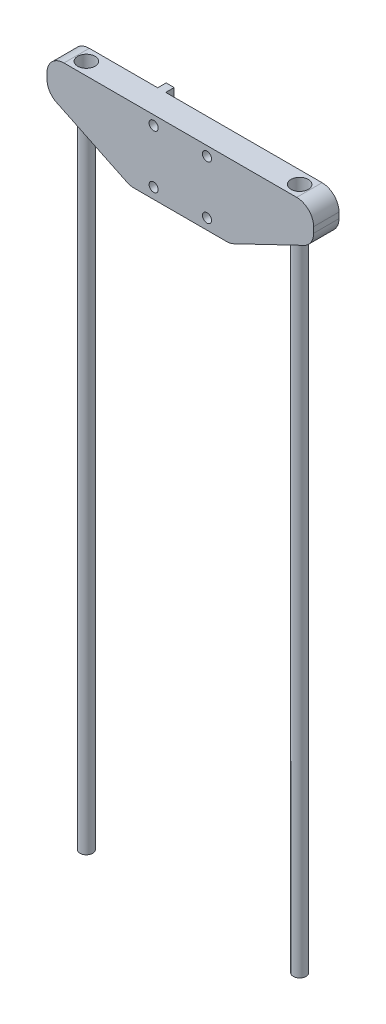
SolidWorks part; units mm, degrees
other "Markup2"
sketch "Sketch8"
other "Markup3"
sketch "Sketch15"
ref_plane "Front Plane" through (0, 0, 0) normal (0, 0, 1) x (1, 0, 0)
ref_plane "Top Plane" through (0, 0, 0) normal (0, 1, 0) x (1, 0, 0)
ref_plane "Right Plane" through (0, 0, 0) normal (1, 0, 0) x (0, 0, -1)
sketch "Sketch2" plane through (0, 0, 0) normal (0, 0, 1) x (1, 0, 0)
  line L0 (-40, 0) -> (-40, -243.6) construction
  line L1 (40, 0) -> (40, -243.6) construction
  line L2 (0, 48.6067) -> (0, -93.2297) construction
  line L3 (-50, 12.5) -> (-50, 0)
  line L4 (-50, 0) -> (-18.75, -15)
  line L5 (-18.75, -15) -> (18.75, -15)
  line L6 (18.75, -15) -> (50, 0)
  line L7 (-50, 12.5) -> (50, 12.5)
  line L8 (50, 12.5) -> (50, 0)
  line L10 (-42.3812, 0) -> (-37.6188, 0)
  line L11 (-42.3812, 0) -> (-42.3812, -243.6)
  line L12 (-42.3812, -243.6) -> (-37.6187, -243.6)
  line L13 (-37.6188, 0) -> (-37.6187, -243.6)
  line L14 (-10, 9) -> (10, 9) construction
  line L15 (-10, 9) -> (-10, -11) construction
  line L16 (-10, -11) -> (10, -11) construction
  line L17 (10, 9) -> (10, -11) construction
  line L18 (37.6188, -243.6) -> (42.3813, -243.6)
  line L19 (37.6188, -243.6) -> (37.6188, 0)
  line L20 (37.6188, 0) -> (42.3812, 0)
  line L21 (42.3813, -243.6) -> (42.3812, 0)
  dimension "D1" = 80
  dimension "D3" = 4.7625
  dimension "D4" = 20
  dimension "D5" = 20
  dimension "D6" = 228.6
  dimension "12.5" = 12.5
  dimension "D8" = 15
  dimension "D9" = 4
  dimension "D10" = 12.5
  dimension "D11" = 100
  dimension "D12" = 37.5
sketch "Sketch9" plane through (0, 0, 0) normal (0, 1, 0) x (1, 0, 0)
  line L0 (-40, 0) -> (-35, 0) construction
  line L2 (-40, 2.3812) -> (-35, 2.3812)
  line L3 (-40, -2.3812) -> (-35, -2.3812)
  line L4 (0, 20.7896) -> (0, -26.7229) construction
  line L5 (40, 0) -> (35, 0) construction
  line L6 (40, 2.3813) -> (35, 2.3813)
  line L7 (40, -2.3813) -> (35, -2.3813)
  line L8 (-37.5, 2.3812) -> (-37.5, -2.3812) construction
  line L9 (-42.3812, 0) -> (-37.6187, 0) construction
  line L10 (37.5, 2.3813) -> (37.5, -2.3813) construction
  arc A0 (-40, 2.3812) -> (-40, -2.3812) centre (-40, 0) ccw
  arc A1 (-35, -2.3812) -> (-35, 2.3812) centre (-35, 0) ccw
  arc A2 (40, 2.3813) -> (40, -2.3813) centre (40, 0) cw
  arc A3 (35, -2.3813) -> (35, 2.3813) centre (35, 0) cw
  circle A4 centre (-40, 0) radius 1.5
  circle A5 centre (40, 0) radius 1.5
  point P5 (-37.5, 0)
  point P15 (37.5, 0)
  dimension "D1" = 5
  dimension "D3" = 3
  dimension "D2" = 4.7625
sketch "Sketch3" plane through (0, 0, 0) normal (0, 0, 1) x (1, 0, 0)
  line L0 (-50, 12.5) -> (-50, 0) construction
  line L1 (-50, 0) -> (-18.75, -15) construction
  line L2 (-18.75, -15) -> (18.75, -15) construction
  line L3 (18.75, -15) -> (50, 0) construction
  line L4 (50, 12.5) -> (50, 0) construction
  line L5 (-50, 12.5) -> (50, 12.5) construction
  line L6 (-50, 12.5) -> (-50, 0)
  line L7 (-50, 0) -> (-18.75, -15)
  line L8 (-18.75, -15) -> (18.75, -15)
  line L9 (18.75, -15) -> (50, 0)
  line L10 (50, 12.5) -> (50, 0)
  line L11 (-50, 12.5) -> (50, 12.5)
extrude "Boss-Extrude1" add sketch "Sketch3" along normal mid plane 9.525
sketch "Sketch10" plane through (0, 0, 0) normal (0, 1, 0) x (1, 0, 0)
  line L0 (40, 2.3813) -> (35, 2.3813) construction
  line L1 (40, -2.3813) -> (35, -2.3813) construction
  line L2 (-40, 2.3812) -> (-35, 2.3812) construction
  line L3 (-40, -2.3812) -> (-35, -2.3812) construction
  line L4 (40, 2.3813) -> (35, 2.3813)
  line L5 (40, -2.3813) -> (35, -2.3813)
  line L6 (-40, 2.3812) -> (-35, 2.3812)
  line L7 (-40, -2.3812) -> (-35, -2.3812)
  arc A0 (35, 2.3813) -> (35, -2.3813) centre (35, 0) ccw construction
  arc A1 (40, -2.3813) -> (40, 2.3813) centre (40, 0) ccw construction
  arc A2 (-35, -2.3812) -> (-35, 2.3812) centre (-35, 0) ccw construction
  arc A3 (-40, 2.3812) -> (-40, -2.3812) centre (-40, 0) ccw construction
  arc A4 (35, 2.3813) -> (35, -2.3813) centre (35, 0) ccw
  arc A5 (40, -2.3813) -> (40, 2.3813) centre (40, 0) ccw
  arc A6 (-35, -2.3812) -> (-35, 2.3812) centre (-35, 0) ccw
  arc A7 (-40, 2.3812) -> (-40, -2.3812) centre (-40, 0) ccw
extrude "Cut-Extrude1" cut sketch "Sketch10" against normal blind 10
sketch "Sketch4" plane through (0, 0, 0) normal (0, 0, 1) x (1, 0, 0)
  line L0 (40, 0) -> (40, -243.6) construction
  line L1 (-40, 0) -> (-40, -243.6) construction
  line L2 (-42.3812, 0) -> (-42.3812, -243.6) construction
  line L3 (-42.3812, -243.6) -> (-37.6187, -243.6) construction
  line L4 (-37.6188, 0) -> (-37.6187, -243.6) construction
  line L5 (-42.3812, 0) -> (-37.6188, 0) construction
  line L6 (40, 0) -> (40, -243.6)
  line L7 (-40, 0) -> (-40, -243.6)
  line L8 (-42.3812, 0) -> (-42.3812, -243.6)
  line L9 (-42.3812, -243.6) -> (-40, -243.6)
  line L10 (-37.6188, 0) -> (-37.6187, -243.6) construction
  line L11 (-42.3812, 0) -> (-40, 0)
  line L12 (-40, -243.6) -> (-40, -275.6996) construction
  line L13 (-40, -243.6) -> (-37.6187, -243.6) construction
  line L14 (-40, 0) -> (-37.6188, 0) construction
  line L15 (40, -243.6) -> (40, -281.3243) construction
  line L16 (37.6188, -243.6) -> (42.3813, -243.6)
  line L17 (37.6188, -243.6) -> (37.6188, 0)
  line L18 (37.6188, 0) -> (42.3812, 0)
  line L19 (42.3813, -243.6) -> (42.3812, 0)
  line L20 (37.6188, -247.4505) -> (40, -247.4505) construction
revolve "Revolve1" add sketch "Sketch4" angle 360 about L12 region at (-41.1906, -121.8, 0)
revolve "Revolve2" add sketch "Sketch4<3>" angle 360 about L15 region at (38.8094, -121.8, 0)
sketch "Sketch4<3>" plane through (0, 0, 0) normal (0, 0, 1) x (1, 0, 0) same geometry as "Sketch4"
hole_wizard "M3 Clearance Hole1" positions "Sketch5" profile "Sketch6" hole size "M3" standard "ANSI Metric" end condition through all
sketch "Sketch5" plane through (0, 0, 4.7625) normal (0, 0, 1) x (1, 0, 0)
  point P0 (-10, 9)
  point P3 (-10, -11)
  point P6 (10, -11)
  point P9 (10, 9)
sketch "Sketch6" plane through (-10, 9, 4.7625) normal (1, 0, 0) x (0, -1, 0)
  line L0 (0, 0) -> (0, 9.525)
  line L1 (0, 9.525) -> (1.7, 9.525)
  line L2 (1.7, 9.525) -> (1.7, 0)
  line L5 (1.7, 0) -> (0, 0)
  line L11 (0, -6.35) -> (0, 107.95) construction
  dimension "Thru Hole Dia." = 3.4
  dimension "Thru Hole Depth" = 9.525
hole_wizard "CBORE for M3 SHCS2" positions "Sketch11" profile "Sketch12" counterbore size "M3" standard "ANSI Metric" end condition through all
sketch "Sketch11" plane through (0, 12.5, 0) normal (0, 1, 0) x (1, 0, 0)
  point P0 (-40, 0)
  point P3 (40, 0)
sketch "Sketch12" plane through (-40, 12.5, 0) normal (1, 0, 0) x (0, 0, 1)
  line L0 (0, 0) -> (0, 256.1)
  line L1 (0, 256.1) -> (1.8, 256.1)
  line L3 (1.8, 256.1) -> (1.8, 11)
  line L4 (1.8, 11) -> (3.25, 11)
  line L5 (3.25, 11) -> (3.25, 0)
  line L7 (3.25, 0) -> (0, 0)
  line L11 (0, -6.35) -> (0, 107.95) construction
  dimension "Thru Hole Dia." = 3.6
  dimension "Thru Hole Depth" = 256.1
  dimension "C'Bore Dia." = 6.5
  dimension "C'Bore Depth" = 11
hole_wizard "M3x0.5 Tapped Hole1" positions "Sketch13" profile "Sketch14" tap size "M3x0.5" standard "ANSI Metric"
sketch "Sketch13" plane through (0, 0, 0) normal (0, 1, 0) x (1, 0, 0)
  point P0 (-40, 0)
  point P3 (40, 0)
sketch "Sketch14" plane through (-40, 0, 0) normal (1, 0, 0) x (0, 0, 1)
  line L0 (0, 0) -> (0, 8.2511)
  line L1 (0, 8.2511) -> (1.25, 7.5)
  line L2 (1.25, 7.5) -> (1.25, 0)
  line L5 (1.25, 0) -> (0, 0)
  line L10 (0, 8.2511) -> (-1.25, 7.5) construction
  line L11 (0, -6.35) -> (0, 107.95) construction
  dimension "Tap Drill Dia." = 2.5
  dimension "Tap Drill Depth" = 7.5
  dimension "Drill Angle" = 118
fillet "Fillet1" radius 6.35 6 edges at (-18.75, -15, 0) (18.75, -15, 0) (50, 0, 0) (50, 12.5, 0) (-50, 12.5, 0) (-50, 0, 0)
sketch "Sketch16" plane through (0, 0, -4.7625) normal (0, 0, -1) x (-1, 0, 0)
  line L0 (-43.65, 12.5) -> (43.65, 12.5) construction
  line L1 (18, -12) -> (15, -12)
  line L2 (18, -12) -> (18, 12.5)
  line L3 (18, 12.5) -> (15, 12.5)
  line L4 (15, -12) -> (15, 12.5)
  line L6 (17.3049, -15) -> (-17.3049, -15) construction
  circle A0 centre (10, -11) radius 1.7 construction
  point P7 (16.5748, -15)
  point P8 (18, -13.5886)
  dimension "D1" = 5
  dimension "D2" = 3
  dimension "D3" = 3
extrude "Boss-Extrude2" add sketch "Sketch16" along normal blind 3.175
